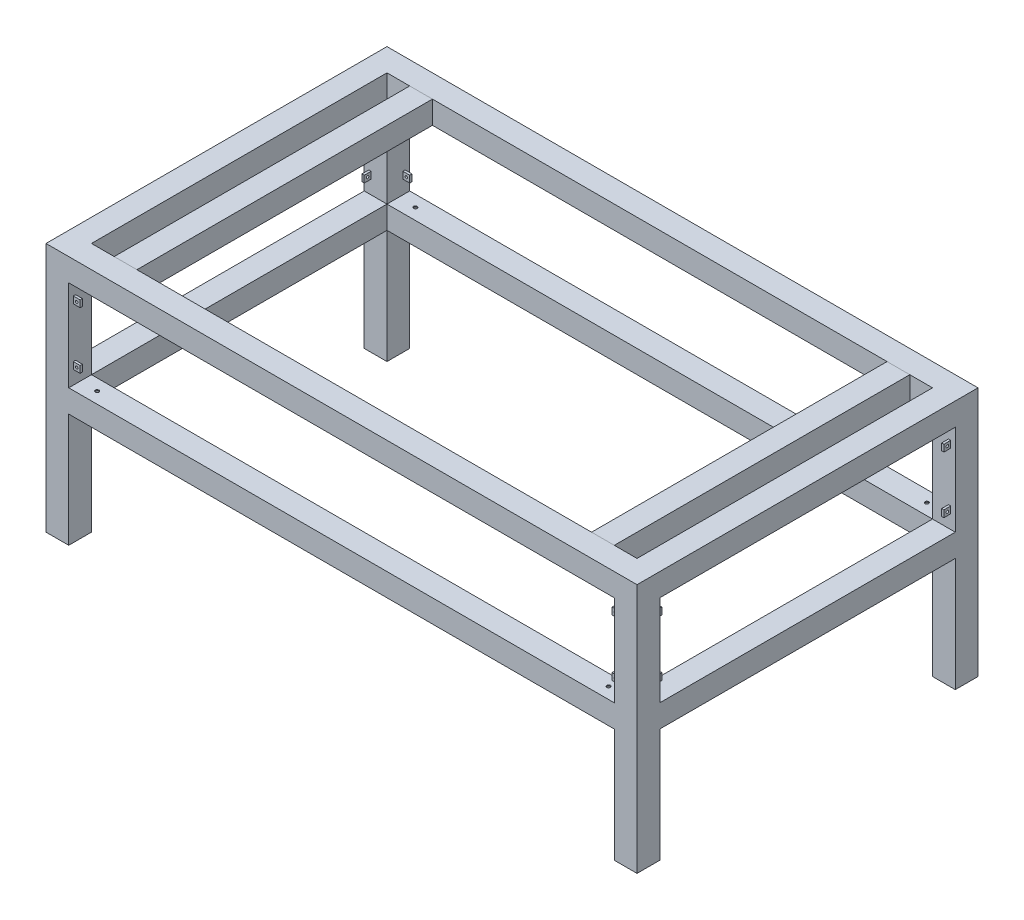
SolidWorks part; units mm, degrees
ref_plane "Plan de face" through (0, 0, 0) normal (0, 0, 1) x (1, 0, 0)
ref_plane "Plan de dessus" through (0, 0, 0) normal (0, 1, 0) x (1, 0, 0)
ref_plane "Plan de droite" through (0, 0, 0) normal (1, 0, 0) x (0, 0, -1)
sketch "Esquisse1" plane through (0, 0, 0) normal (0, 1, 0) x (1, 0, 0)
  line L1 (0, 0) -> (1300, 0)
  line L2 (0, 0) -> (0, 750)
  line L3 (0, 750) -> (1300, 750)
  line L4 (1300, 0) -> (1300, 750)
  line L5 (50, 700) -> (1250, 700)
  line L6 (50, 700) -> (50, 50)
  line L7 (50, 50) -> (1250, 50)
  line L8 (1250, 700) -> (1250, 50)
  dimension "D1" = 1300
  dimension "D2" = 750
  dimension "D3" = 50
  dimension "D4" = 50
  dimension "D5" = 50
  dimension "D6" = 50
extrude "Boss.-Extru.1" add sketch "Esquisse1" against normal blind 550
sketch "Esquisse2" plane through (0, 0, 0) normal (0, 0, 1) x (1, 0, 0)
  line L0 (0, 0) -> (1300, 0) construction
  line L1 (50, -50) -> (1250, -50)
  line L2 (50, -50) -> (50, -250)
  line L3 (50, -250) -> (1250, -250)
  line L4 (1250, -50) -> (1250, -250)
  line L5 (50, -300) -> (1250, -300)
  line L6 (50, -300) -> (50, -550)
  line L7 (50, -550) -> (1250, -550)
  line L8 (1250, -300) -> (1250, -550)
  line L9 (0, -550) -> (1300, -550) construction
  line L10 (1300, -550) -> (1300, 0) construction
  line L11 (0, -550) -> (0, 0) construction
  point P12 (1250, -425)
  dimension "D1" = 50
  dimension "D2" = 50
  dimension "D3" = 200
  dimension "D4" = 0
  dimension "D5" = 50
  dimension "D6" = 50
  dimension "D7" = 50
  dimension "D8" = 50
extrude "Enlèv. mat.-Extru.1" cut sketch "Esquisse2" against normal through all
sketch "Esquisse3" plane through (0, 0, 0) normal (-1, 0, 0) x (0, 0, 1)
  line L0 (-750, -550) -> (0, -550) construction
  line L1 (-700, -50) -> (-50, -50)
  line L2 (-700, -50) -> (-700, -250)
  line L3 (-700, -250) -> (-50, -250)
  line L4 (-50, -50) -> (-50, -250)
  line L5 (-700, -300) -> (-50, -300)
  line L6 (-700, -300) -> (-700, -550)
  line L7 (-700, -550) -> (-50, -550)
  line L8 (-50, -300) -> (-50, -550)
  line L9 (-750, 0) -> (0, 0) construction
  line L10 (0, -550) -> (0, 0) construction
  line L11 (-750, -550) -> (-750, 0) construction
  dimension "D1" = 50
  dimension "D2" = 50
  dimension "D3" = 50
  dimension "D4" = 50
  dimension "D5" = 50
  dimension "D6" = 200
  dimension "D7" = 50
extrude "Enlèv. mat.-Extru.2" cut sketch "Esquisse3" against normal through all
sketch "Esquisse4" plane through (0, 0, 0) normal (0, 1, 0) x (1, 0, 0)
  line L0 (1250, 700) -> (50, 700) construction
  line L1 (100, 700) -> (150, 700)
  line L2 (100, 700) -> (100, 50)
  line L3 (100, 50) -> (150, 50)
  line L4 (150, 700) -> (150, 50)
  line L5 (50, 50) -> (1250, 50) construction
  line L6 (50, 700) -> (50, 50) construction
  line L7 (1150, 700) -> (1200, 700)
  line L8 (1150, 700) -> (1150, 50)
  line L9 (1150, 50) -> (1200, 50)
  line L10 (1200, 700) -> (1200, 50)
  line L11 (1250, 50) -> (1250, 700) construction
  dimension "D1" = 50
  dimension "D2" = 50
  dimension "D3" = 50
  dimension "D4" = 50
extrude "Boss.-Extru.2" add sketch "Esquisse4" against normal blind 50 separate body
sketch "Esquisse5" plane through (1250, 0, 0) normal (-1, 0, 0) x (0, 0, 1)
  line L0 (-750, -250) -> (-750, -50) construction
  line L1 (-750, -80) -> (-735, -80)
  line L2 (-750, -80) -> (-750, -95)
  line L3 (-750, -95) -> (-735, -95)
  line L4 (-735, -80) -> (-735, -95)
  line L5 (-740, -80) -> (-740, -95)
  line L6 (-750, -205) -> (-735, -205)
  line L7 (-750, -205) -> (-750, -220)
  line L8 (-750, -220) -> (-735, -220)
  line L9 (-735, -205) -> (-735, -220)
  line L10 (-740, -205) -> (-740, -220)
  line L11 (-750, -50) -> (-700, -50) construction
  line L12 (-750, -250) -> (-700, -250) construction
  dimension "D1" = 10
  dimension "D2" = 5
  dimension "D3" = 5
  dimension "D4" = 15
  dimension "D5" = 15
  dimension "D6" = 30
  dimension "D7" = 30
extrude "Boss.-Extru.3" add sketch "Esquisse5" along normal blind 15 contours L1 L5 L3 L4 | L6 L10 L8 L9 region at (1250, -87.5, -737.5) region at (1250, -212.5, -737.5)
sketch "Esquisse6" plane through (0, 0, -700) normal (0, 0, 1) x (1, 0, 0)
  line L0 (1300, -50) -> (1300, -250) construction
  line L1 (1300, -80) -> (1285, -80)
  line L2 (1300, -80) -> (1300, -95)
  line L3 (1300, -95) -> (1285, -95)
  line L4 (1285, -80) -> (1285, -95)
  line L5 (1290, -80) -> (1290, -95)
  line L6 (1300, -220) -> (1285, -220)
  line L7 (1300, -220) -> (1300, -205)
  line L8 (1300, -205) -> (1285, -205)
  line L9 (1285, -220) -> (1285, -205)
  line L10 (1290, -205) -> (1290, -220)
  line L11 (1300, -50) -> (1250, -50) construction
  line L12 (1300, -250) -> (1250, -250) construction
  point P18 (1292.5, -220)
  dimension "D1" = 15
  dimension "D2" = 15
  dimension "D3" = 5
  dimension "D4" = 5
  dimension "D5" = 10
  dimension "D6" = 30
  dimension "D7" = 30
extrude "Boss.-Extru.4" add sketch "Esquisse6" along normal blind 15 contours L5 L1 L4 L3 | L10 L8 L9 L6 region at (1287.5, -87.5, -700) region at (1287.5, -212.5, -700)
sketch "Esquisse7" plane through (50, 0, 0) normal (1, 0, 0) x (0, 0, -1)
  line L0 (750, -50) -> (750, -250) construction
  line L1 (750, -80) -> (735, -80)
  line L2 (750, -80) -> (750, -95)
  line L3 (750, -95) -> (735, -95)
  line L4 (735, -80) -> (735, -95)
  line L5 (740, -80) -> (740, -95)
  line L6 (750, -220) -> (735, -220)
  line L7 (750, -220) -> (750, -205)
  line L8 (750, -205) -> (735, -205)
  line L9 (735, -220) -> (735, -205)
  line L10 (740, -205) -> (740, -220)
  line L11 (750, -250) -> (700, -250) construction
  line L12 (750, -50) -> (700, -50) construction
  dimension "D1" = 15
  dimension "D2" = 15
  dimension "D3" = 10
  dimension "D4" = 5
  dimension "D5" = 5
  dimension "D6" = 30
  dimension "D7" = 30
extrude "Boss.-Extru.5" add sketch "Esquisse7" along normal blind 15 contours L5 L1 L4 L3 | L10 L8 L9 L6 region at (50, -87.5, -737.5) region at (50, -212.5, -737.5)
sketch "Esquisse8" plane through (0, 0, -700) normal (0, 0, 1) x (1, 0, 0)
  line L0 (0, -50) -> (0, -250) construction
  line L1 (10, -80) -> (10, -95)
  line L2 (0, -80) -> (15, -80)
  line L3 (0, -80) -> (0, -95)
  line L4 (0, -95) -> (15, -95)
  line L5 (15, -80) -> (15, -95)
  line L6 (0, -205) -> (15, -205)
  line L7 (0, -205) -> (0, -220)
  line L8 (0, -220) -> (15, -220)
  line L9 (15, -205) -> (15, -220)
  line L10 (10, -205) -> (10, -220)
  line L11 (50, -250) -> (0, -250) construction
  line L13 (50, -50) -> (0, -50) construction
  point P16 (7.5, -220)
  dimension "D1" = 15
  dimension "D2" = 5
  dimension "D3" = 10
  dimension "D4" = 30
  dimension "D5" = 5
  dimension "D6" = 10
  dimension "D7" = 15
  dimension "D8" = 30
extrude "Boss.-Extru.6" add sketch "Esquisse8" along normal blind 15 contours L5 L2 L1 L4 | L6 L10 L8 L9 region at (12.5, -87.5, -700) region at (12.5, -212.5, -700)
sketch "Esquisse10" plane through (50, 0, 0) normal (1, 0, 0) x (0, 0, -1)
  line L0 (0, -50) -> (0, -250) construction
  line L1 (0, -80) -> (15, -80)
  line L2 (0, -80) -> (0, -95)
  line L3 (0, -95) -> (15, -95)
  line L4 (15, -80) -> (15, -95)
  line L5 (10, -80) -> (10, -95)
  line L6 (0, -205) -> (15, -205)
  line L7 (0, -205) -> (0, -220)
  line L8 (0, -220) -> (15, -220)
  line L9 (15, -205) -> (15, -220)
  line L10 (10, -205) -> (10, -220)
  line L11 (50, -250) -> (0, -250) construction
  line L12 (50, -50) -> (0, -50) construction
  point P18 (7.5, -80)
  dimension "D1" = 5
  dimension "D2" = 5
  dimension "D3" = 15
  dimension "D4" = 15
  dimension "D5" = 15
  dimension "D6" = 15
  dimension "D7" = 30
  dimension "D8" = 30
extrude "Boss.-Extru.7" add sketch "Esquisse10" along normal blind 15 contours L1 L5 L3 L4 | L6 L10 L8 L9 region at (50, -87.5, -12.5) region at (50, -212.5, -12.5)
sketch "Esquisse12" plane through (0, 0, -50) normal (0, 0, -1) x (-1, 0, 0)
  line L0 (0, -250) -> (0, -50) construction
  line L1 (0, -80) -> (-15, -80)
  line L2 (0, -80) -> (0, -95)
  line L3 (0, -95) -> (-15, -95)
  line L4 (-15, -80) -> (-15, -95)
  line L5 (-10, -80) -> (-10, -95)
  line L6 (0, -205) -> (-15, -205)
  line L7 (0, -205) -> (0, -220)
  line L8 (0, -220) -> (-15, -220)
  line L9 (-15, -205) -> (-15, -220)
  line L10 (-10, -205) -> (-10, -220)
  line L11 (-50, -50) -> (0, -50) construction
  line L12 (-50, -250) -> (0, -250) construction
  point P14 (-15, -87.5)
  dimension "D1" = 15
  dimension "D2" = 15
  dimension "D3" = 15
  dimension "D4" = 15
  dimension "D5" = 5
  dimension "D6" = 5
  dimension "D7" = 30
  dimension "D8" = 30
extrude "Boss.-Extru.8" add sketch "Esquisse12" along normal blind 15 contours L5 L1 L4 L3 | L10 L6 L9 L8 region at (12.5, -87.5, -50) region at (12.5, -212.5, -50)
sketch "Esquisse14" plane through (1250, 0, 0) normal (-1, 0, 0) x (0, 0, 1)
  line L0 (0, -250) -> (0, -50) construction
  line L1 (0, -80) -> (-15, -80)
  line L2 (0, -80) -> (0, -95)
  line L3 (0, -95) -> (-15, -95)
  line L4 (-15, -80) -> (-15, -95)
  line L5 (-10, -80) -> (-10, -95)
  line L6 (0, -205) -> (-15, -205)
  line L7 (0, -205) -> (0, -220)
  line L8 (0, -220) -> (-15, -220)
  line L9 (-15, -205) -> (-15, -220)
  line L10 (-10, -205) -> (-10, -220)
  line L11 (-50, -250) -> (0, -250) construction
  line L12 (-50, -50) -> (0, -50) construction
  point P18 (-15, -87.5)
  dimension "D1" = 15
  dimension "D2" = 5
  dimension "D3" = 15
  dimension "D4" = 30
  dimension "D5" = 30
  dimension "D6" = 5
  dimension "D7" = 15
  dimension "D8" = 15
extrude "Boss.-Extru.9" add sketch "Esquisse14" along normal blind 15 contours L5 L1 L4 L3 | L10 L6 L9 L8 region at (1250, -87.5, -12.5) region at (1250, -212.5, -12.5)
sketch "Esquisse15" plane through (0, 0, -50) normal (0, 0, -1) x (-1, 0, 0)
  line L0 (-1300, -250) -> (-1300, -50) construction
  line L1 (-1300, -80) -> (-1285, -80)
  line L2 (-1300, -80) -> (-1300, -95)
  line L3 (-1300, -95) -> (-1285, -95)
  line L4 (-1285, -80) -> (-1285, -95)
  line L5 (-1290, -80) -> (-1290, -95)
  line L6 (-1300, -205) -> (-1285, -205)
  line L7 (-1300, -205) -> (-1300, -220)
  line L8 (-1300, -220) -> (-1285, -220)
  line L9 (-1285, -205) -> (-1285, -220)
  line L10 (-1290, -205) -> (-1290, -220)
  line L11 (-1300, -50) -> (-1250, -50) construction
  line L12 (-1300, -250) -> (-1250, -250) construction
  point P14 (-1285, -212.5)
  point P15 (-1300, -212.5)
  dimension "D1" = 15
  dimension "D2" = 15
  dimension "D3" = 15
  dimension "D4" = 5
  dimension "D5" = 15
  dimension "D6" = 30
  dimension "D7" = 30
extrude "Boss.-Extru.10" add sketch "Esquisse15" along normal blind 15 contours L6 L10 L8 L9 | L1 L5 L3 L4 region at (1287.5, -87.5, -50) region at (1287.5, -212.5, -50)
sketch "Esquisse16" plane through (1290, 0, 0) normal (1, 0, 0) x (0, 0, -1)
  line L0 (65, -95) -> (50, -95) construction
  line L1 (65, -80) -> (50, -80) construction
  line L2 (65, -80) -> (65, -95) construction
  line L3 (50, -80) -> (50, -95) construction
  line L4 (65, -205) -> (65, -220) construction
  line L5 (65, -220) -> (50, -220) construction
  line L6 (685, -80) -> (685, -95) construction
  line L7 (685, -80) -> (700, -80) construction
  line L8 (685, -205) -> (685, -220) construction
  line L9 (685, -205) -> (700, -205) construction
  circle A0 centre (57.5, -87.5) radius 2.75
  circle A1 centre (57.5, -212.5) radius 2.75
  circle A2 centre (692.5, -87.5) radius 2.75
  circle A3 centre (692.5, -212.5) radius 2.75
  dimension "D5" = 5.5
  dimension "D6" = 5.5
  dimension "D9" = 5.5
  dimension "D12" = 5.5
  dimension "D1" = 15
  dimension "D2" = 7.5
  dimension "D3" = 15
  dimension "D4" = 7.5
  dimension "D7" = 7.5
  dimension "D8" = 7.5
  dimension "D10" = 7.5
  dimension "D11" = 7.5
  dimension "D13" = 7.5
  dimension "D14" = 7.5
extrude "Enlèv. mat.-Extru.3" cut sketch "Esquisse16" against normal blind 1500
sketch "Esquisse17" plane through (0, 0, -10) normal (0, 0, 1) x (1, 0, 0)
  line L0 (65, -205) -> (50, -205) construction
  line L1 (65, -205) -> (65, -220) construction
  line L2 (65, -80) -> (50, -80) construction
  line L3 (65, -80) -> (65, -95) construction
  line L4 (1235, -80) -> (1235, -95) construction
  line L5 (1235, -95) -> (1250, -95) construction
  line L6 (1235, -205) -> (1250, -205) construction
  line L8 (1235, -205) -> (1235, -220) construction
  circle A0 centre (57.5, -87.5) radius 2.75
  circle A1 centre (57.5, -212.5) radius 2.75
  circle A2 centre (1242.5, -212.5) radius 2.75
  circle A3 centre (1242.5, -87.5) radius 2.75
  dimension "D1" = 5.5
  dimension "D2" = 5.5
  dimension "D3" = 5.5
  dimension "D4" = 5.5
  dimension "D5" = 7.5
  dimension "D6" = 7.5
  dimension "D7" = 7.5
  dimension "D8" = 7.5
  dimension "D9" = 7.5
  dimension "D10" = 7.5
  dimension "D11" = 7.5
  dimension "D12" = 7.5
extrude "Enlèv. mat.-Extru.4" cut sketch "Esquisse17" against normal blind 1000
sketch "Esquisse18" plane through (0, -250, 0) normal (0, 1, 0) x (1, 0, 0)
  line L0 (50, 0) -> (1250, 0) construction
  line L1 (50, 750) -> (1250, 750) construction
  line L2 (1250, 750) -> (1250, 700) construction
  line L3 (50, 750) -> (50, 700) construction
  line L4 (1250, 50) -> (1250, 0) construction
  line L5 (50, 50) -> (50, 0) construction
  circle A0 centre (1212.5, 25) radius 4
  circle A1 centre (87.5, 25) radius 4
  circle A2 centre (87.5, 725) radius 4
  circle A3 centre (1212.5, 725) radius 4
  dimension "D1" = 8
  dimension "D2" = 8
  dimension "D3" = 8
  dimension "D4" = 8
  dimension "D5" = 1125
  dimension "D6" = 1125
  dimension "D7" = 25
  dimension "D8" = 25
  dimension "D9" = 25
  dimension "D10" = 25
  dimension "D11" = 700
  dimension "D12" = 700
  dimension "D13" = 37.5
  dimension "D14" = 37.5
  dimension "D15" = 37.5
  dimension "D16" = 37.5
extrude "Enlèv. mat.-Extru.5" cut sketch "Esquisse18" against normal blind 80
sketch "Esquisse19" plane through (0, -300, 0) normal (0, -1, 0) x (-1, 0, 0)
  circle A0 centre (-1212.5, 725) radius 15
  circle A1 centre (-87.5, 725) radius 15
  circle A2 centre (-87.5, 25) radius 15
  circle A3 centre (-1212.5, 25) radius 15
  dimension "D1" = 30
  dimension "D2" = 30
  dimension "D3" = 30
  dimension "D4" = 30
extrude "Enlèv. mat.-Extru.6" cut sketch "Esquisse19" against normal blind 48
